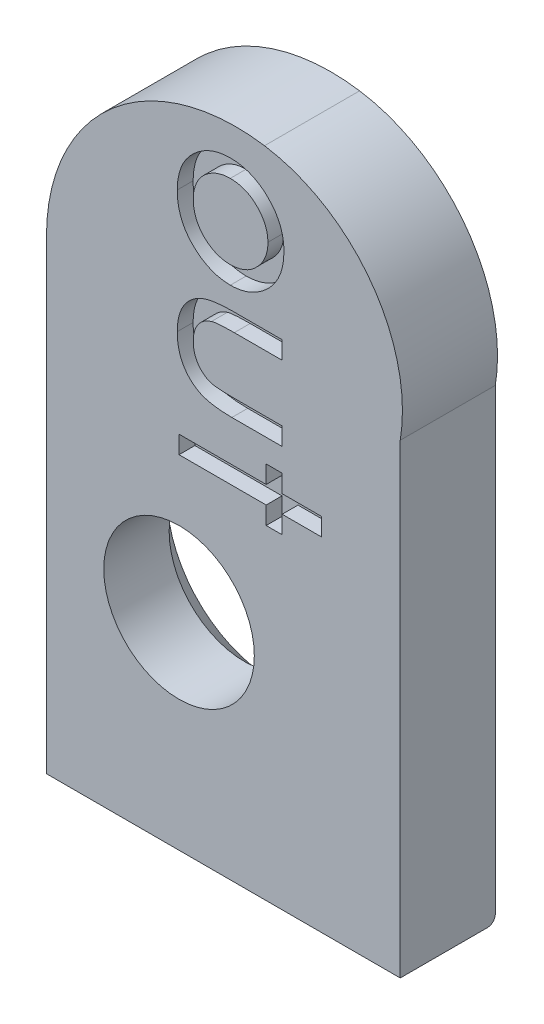
SolidWorks part; units mm, degrees
ref_plane "Front Plane" through (0, 0, 0) normal (0, 0, 1) x (1, 0, 0)
ref_plane "Top Plane" through (0, 0, 0) normal (0, 1, 0) x (1, 0, 0)
ref_plane "Right Plane" through (0, 0, 0) normal (1, 0, 0) x (0, 0, -1)
sketch "Sketch1" plane through (0, 0, 0) normal (0, 0, 1) x (1, 0, 0)
  line L0 (0, 0) -> (10.3566, 0) construction
  line L1 (0, 0) -> (6.5503, 11.3454) construction
  line L4 (-3.3457, 6.553) -> (-3.3457, -5.2)
  line L5 (-3.3457, -5.2) -> (5.5829, -5.2)
  line L6 (5.5829, 6.553) -> (5.5829, -5.2)
  arc A1 (-3.3457, 6.553) -> (2.157, 11.2786) centre (1.4348, 6.553) cw
  arc A2 (2.157, 11.2786) -> (5.5829, 6.553) centre (1.5375, 7.2249) cw
  dimension "D2" = 5.2
  dimension "D1" = 60
extrude "Boss-Extrude1" add sketch "Sketch1" along normal blind 2.4
sketch "Sketch3" plane through (0, 0, 0) normal (0, 0, 1) x (1, 0, 0)
  circle A0 centre (0, 0) radius 1.9
extrude "Cut-Extrude3" cut sketch "Sketch3" along normal through all
chamfer "Chamfer1" distance 0.75 angle 47 1 edges at (1.9, 0, 0) first distance on face at (1.9, 0, 2.4)
fillet "Fillet1" radius 0.2 1 edges at (1.1186, -5.2, 0)
ref_plane "Plane1" through (0, 0, 2.4) normal (0, 0, 1) x (1, 0, 0)
sketch "Sketch4" plane through (0, 0, 2.4) normal (0, 0, 1) x (1, 0, 0)
  line L0 (0, 10.8057) -> (0, 2.2646) construction
  text T0 "<b>out</b>"
extrude "Cut-Extrude4" cut sketch "Sketch4" against normal blind 0.4
scale "Scale1" scale about centroid uniform scaling yes scale factor 1.15
